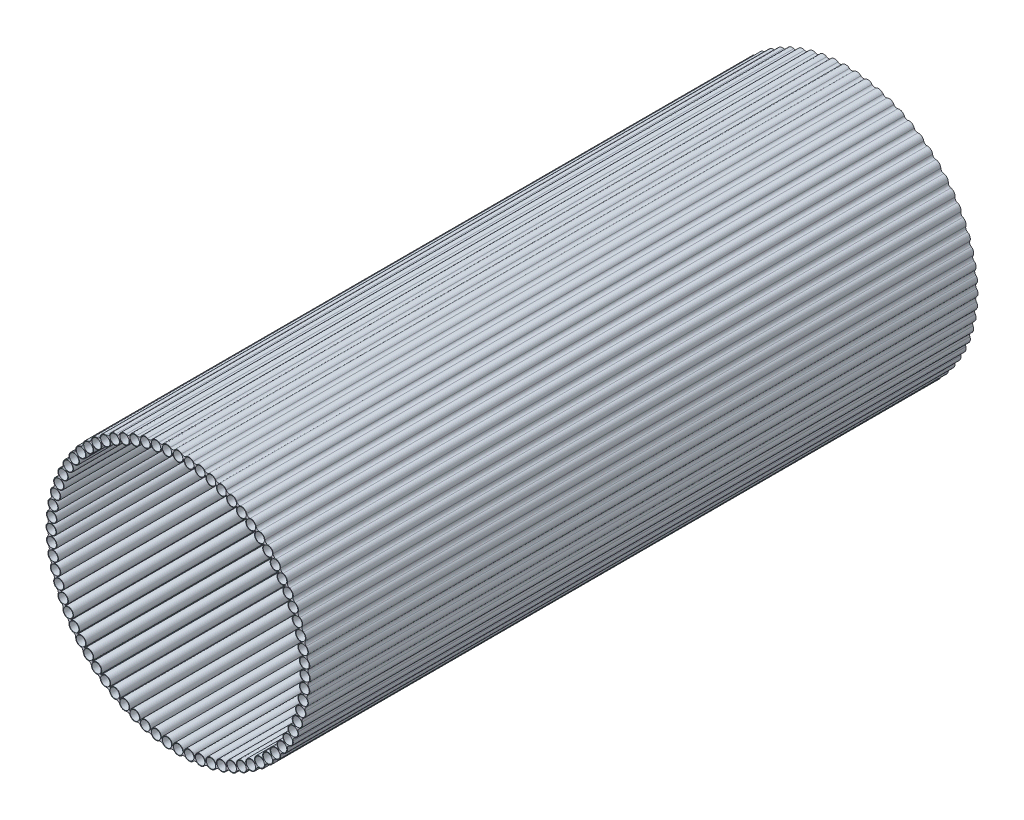
SolidWorks part; units mm, degrees
ref_plane "Front Plane" through (0, 0, 0) normal (1, 0, 0) x (0, 1, 0)
ref_plane "Top Plane" through (0, 0, 0) normal (0, 0, 1) x (0, 1, 0)
ref_plane "Right Plane" through (0, 0, 0) normal (0, 1, 0) x (-1, 0, 0)
sketch "Sketch1" plane through (0, 0, 0) normal (0, 0, 1) x (0, 1, 0)
  line L0 (5.0496, 57.7169) -> (0, 0) construction
  line L1 (0, 57.9374) -> (0, 0) construction
  circle A0 centre (0, 0) radius 60.325 construction
  circle A1 centre (0, 57.9374) radius 2.3876
  circle A2 centre (0, 57.9374) radius 2.1336
  circle A3 centre (5.0496, 57.7169) radius 2.3876
  arc A4 (2.3876, 57.9374) -> (2.6711, 57.925) centre (0, 0) cw
  arc A5 (1.6298, 59.6823) -> (3.5781, 59.5972) centre (2.6536, 60.7785) ccw
  point P13 (0, 0)
  dimension "D1" = 120.65
  dimension "D2" = 4.7752
  dimension "D3" = 4.2672
  dimension "D5" = 1.5
  dimension "D4" = 5
extrude "Boss-Extrude1" add sketch "Sketch1" along normal blind 304.8 contours A1 A2 | A5 A1 A4 A3 region at (-57.0131, -2.128, 0) region at (-58.8368, 2.5689, 0)
ref_axis "Axis1" through (0, 0, 320.04) along (0, 0, -1)
pattern_circular "CirPattern1" count 72 over 360 about axis through (0, 0, 320.04) along (0, 0, -1) of "Boss-Extrude1"
